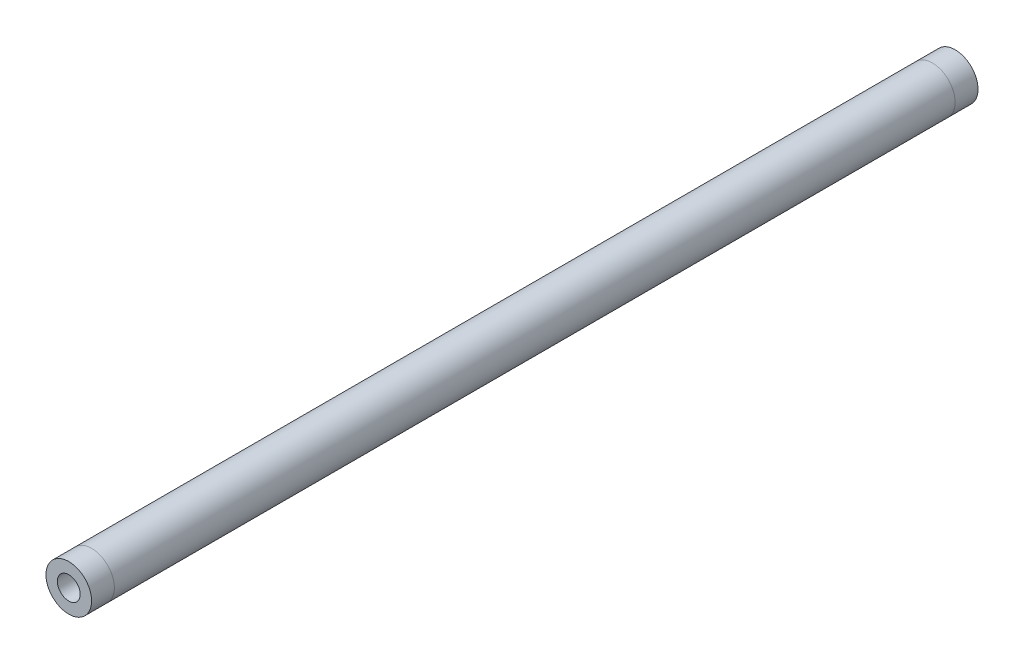
SolidWorks part; units mm, degrees
material "AISI 4130 Steel, normalized at 870C"
ref_plane "Front Plane" through (0, 0, 0) normal (0, 0, 1) x (1, 0, 0)
ref_plane "Top Plane" through (0, 0, 0) normal (0, 1, 0) x (1, 0, 0)
ref_plane "Right Plane" through (0, 0, 0) normal (1, 0, 0) x (0, 0, -1)
sketch "Axis" plane through (0, 0, 0) normal (1, 0, 0) x (0, 0, -1)
  line L0 (0, 0) -> (246.6988, 0) construction
  line L1 (246.6988, 0) -> (240.3488, 0)
  line L2 (246.6988, 0) -> (268.6063, 0) construction
  line L3 (0, 0) -> (-21.9075, 0) construction
  line L4 (-21.9075, 0) -> (-95.3875, 0)
  point P4 (0, 0)
  point P5 (246.6988, 0)
  point P6 (240.3488, 0)
  dimension "D1" = 6.35
  dimension "D2" = 21.9075
  dimension "D3" = 21.9075
sketch "Sketch1" plane through (0, 0, 0) normal (0, 0, 1) x (1, 0, 0)
  circle A0 centre (0, 0) radius 6.35
  circle A1 centre (0, 0) radius 5.461
  circle A2 centre (0, 0) radius 3.175
  dimension "D1" = 12.7
  dimension "D2" = 0.889
  dimension "D3" = 6.35
extrude "Threaded insert 1-1" add sketch "Sketch1" against normal blind 6.35 contours A0 A1 | A1 A2 region at (-6.1704, 0, 0) region at (-5.3065, 0, 0)
extrude "Threaded insert 1-2" add sketch "Sketch1<3>" against normal blind 6.35 from surface contours A1 A2 region at (-5.3065, 0, 0) starting at face at (6.35, 0, -6.35)
sketch "Sketch1<3>" plane through (0, 0, 0) normal (0, 0, 1) x (1, 0, 0) same geometry as "Sketch1"
extrude "Tube extrude" add sketch "Sketch1<4>" against normal up to vertex (240.3488 mm away) from surface separate body contours A0 A1 region at (-6.1704, 0, 0) up to point (0, 0, -240.3488) starting at face at (5.461, 0, -6.35)
sketch "Sketch1<4>" plane through (0, 0, 0) normal (0, 0, 1) x (1, 0, 0) same geometry as "Sketch1"
extrude "Threaded insert 2-1" add sketch "Sketch1<6>" along normal blind 6.35 from surface separate body contours A1 A2 region at (-5.3065, 0, 0) starting at face at (5.461, 0, -240.3488)
sketch "Sketch1<6>" plane through (0, 0, 0) normal (0, 0, 1) x (1, 0, 0) same geometry as "Sketch1"
extrude "Threaded insert 2-2" add sketch "Sketch1<9>" against normal blind 6.35 from surface separate body contours A1 A2 | A0 A1 region at (-6.1704, 0, 0) region at (-5.3065, 0, 0) starting at face at (5.461, 0, -240.3488)
sketch "Sketch1<9>" plane through (0, 0, 0) normal (0, 0, 1) x (1, 0, 0) same geometry as "Sketch1"
combine bodies "Combine1" operation type add bodies to combine 106 104
equation "\"Threaded insert outer thickness\"= .25"
equation "\"D1@Threaded insert 1-1\"=\"Threaded insert outer thickness\""
equation "\"D1@Threaded insert 2-2\"=\"Threaded insert outer thickness\""
equation "\"D1@Axis\" = \"Threaded insert outer thickness\""
